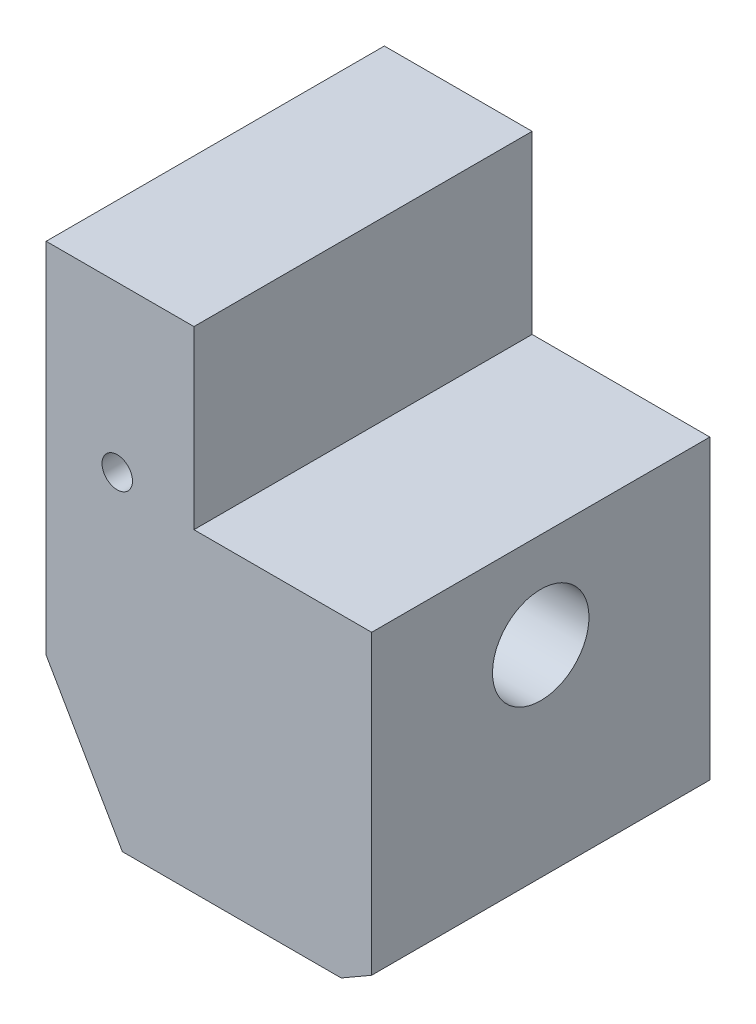
SolidWorks part; units mm, degrees
ref_plane "Front Plane" through (0, 0, 0) normal (0, 0, 1) x (1, 0, 0)
ref_plane "Top Plane" through (0, 0, 0) normal (0, 1, 0) x (1, 0, 0)
ref_plane "Right Plane" through (0, 0, 0) normal (1, 0, 0) x (0, 0, -1)
sketch "Sketch1" plane through (0, 0, 0) normal (1, 0, 0) x (0, 0, -1)
  line L1 (-16.65, 24.15) -> (16.65, 24.15)
  line L2 (-16.65, 24.15) -> (-16.65, -24.15)
  line L3 (-16.65, -24.15) -> (16.65, -24.15)
  line L4 (16.65, 24.15) -> (16.65, -24.15)
  line L5 (-16.65, 24.15) -> (16.65, -24.15) construction
  line L6 (-16.65, -24.15) -> (16.65, 24.15) construction
  point P0 (0, 0)
  dimension "D1" = 48.3
  dimension "D2" = 33.3
extrude "Boss-Extrude1" add sketch "Sketch1" along normal blind 9.55
sketch "Sketch2" plane through (0, 0, 0) normal (-1, 0, 0) x (0, 0, 1)
  line L0 (0, 24.15) -> (0, 19.15) construction
  line L3 (-16.65, 24.15) -> (16.65, 24.15) construction
  line L4 (0, 19.15) -> (0, -19.451) construction
  line L5 (0, -19.451) -> (0, -24.15) construction
  line L6 (16.65, -24.15) -> (-16.65, -24.15) construction
  line L7 (0, 19.15) -> (-5.65, 19.15)
  line L8 (-5.65, 19.15) -> (-5.65, 5.45)
  line L9 (-5.65, 5.45) -> (-11.65, -0.9874)
  line L10 (-11.65, -0.9874) -> (-11.65, -9.1)
  line L11 (-11.65, -9.1) -> (-10.5771, -10.1)
  line L12 (-10.5771, -10.1) -> (10.5771, -10.1)
  line L13 (11.65, -9.1) -> (10.5771, -10.1)
  line L14 (11.65, -0.9874) -> (11.65, -9.1)
  line L15 (5.65, 5.45) -> (11.65, -0.9874)
  line L16 (5.65, 5.45) -> (5.65, 11.45)
  line L17 (5.65, 11.45) -> (4.5, 12.6)
  line L18 (4.5, 12.6) -> (4.5, 19.15)
  line L19 (4.5, 19.15) -> (0, 19.15)
  point P16 (0, -10.1)
  dimension "D1" = 5
  dimension "D2" = 4.699
  dimension "D3" = 11.65
  dimension "D4" = 15.55
  dimension "D5" = 5.65
  dimension "D6" = 13.7
  dimension "D7" = 8.8
  dimension "D8" = 1
  dimension "D9" = 6
  dimension "D10" = 7.15
  dimension "D11" = 4.5
extrude "Cut-Extrude1" cut sketch "Sketch2" against normal blind 5
sketch "Sketch3" plane through (5, 0, 0) normal (-1, 0, 0) x (0, 0, 1)
  line L0 (-5.65, 19.15) -> (4.5, 19.15)
  line L1 (4.5, 19.15) -> (4.5, 12.6)
  line L2 (4.5, 12.6) -> (5.65, 11.45)
  line L3 (5.65, 11.45) -> (5.65, 5.45)
  line L4 (5.65, 5.45) -> (-5.65, 5.45)
  line L5 (-5.65, 5.45) -> (-5.65, 19.15)
extrude "Cut-Extrude2" cut sketch "Sketch3" against normal blind 4.5
sketch "Sketch5" plane through (9.55, 0, 0) normal (1, 0, 0) x (0, 0, -1)
  line L1 (-16.65, 24.15) -> (16.65, 24.15)
  line L2 (-16.65, 24.15) -> (-16.65, -24.15)
  line L3 (-16.65, -24.15) -> (16.65, -24.15)
  line L4 (16.65, 24.15) -> (16.65, -24.15)
  line L5 (-16.65, 24.15) -> (16.65, -24.15) construction
  line L6 (-16.65, -24.15) -> (16.65, 24.15) construction
  point P0 (0, 0)
extrude "Boss-Extrude3" add sketch "Sketch5" along normal blind 22.5
sketch "Sketch6" plane through (5, 0, 0) normal (-1, 0, 0) x (0, 0, 1)
  line L0 (0, 5.45) -> (0, -2.575) construction
  line L1 (-5.65, 5.45) -> (5.65, 5.45) construction
  line L2 (0, 1.45) -> (5.4752, 1.45) construction
  circle A0 centre (0, -2.575) radius 4.025
  dimension "D2" = 8.05
  dimension "D1" = 4
extrude "Cut-Extrude3" cut sketch "Sketch6" against normal blind 12
sketch "Sketch7" plane through (17, 0, 0) normal (-1, 0, 0) x (0, 0, 1)
  circle A0 centre (0, -2.575) radius 4.75
  dimension "D1" = 9.5
extrude "Cut-Extrude4" cut sketch "Sketch7" against normal up to surface (15.05 mm away) up to face at (32.05, 0, 0)
sketch "Sketch27" plane through (0, 0, 5.65) normal (0, 0, -1) x (-1, 0, 0)
  line L0 (-9.5, 5.45) -> (-9.5, 11.45) construction
  line L1 (-9.5, 5.45) -> (-5, 5.45) construction
  circle A0 centre (-7, 7.95) radius 1.5
  dimension "D1" = 3
  dimension "D2" = 2.5
  dimension "D3" = 2.5
extrude "Cut-Extrude6" cut sketch "Sketch27" against normal through all both and the other way through all
ref_plane "Plane1" through (18.4698, -31.9906, 0) normal (0.5, -0.866, 0) x (0, 0, -1)
sketch "Sketch28" plane through (0, 0, 0) normal (0, 0, 1) x (1, 0, 0)
  line L0 (32.05, -2.575) -> (17, -2.575) construction
  line L1 (32.05, -7.325) -> (32.05, 2.175) construction
  line L2 (17, -6.6) -> (17, 1.45) construction
  line L3 (17, -2.575) -> (17, -6.6) construction
  line L4 (17, -7.325) -> (17, 2.175) construction
  line L5 (17, -6.6) -> (13, -6.6) construction
  line L6 (13, -6.6) -> (25.3619, -28.0114)
  line L7 (3.2039, -40.8043) -> (33.7356, -23.1768) construction
  line L8 (13, -6.6) -> (10.75, -2.7029)
  dimension "D1" = 4.025
  dimension "D2" = 4
  dimension "D3" = 60
  dimension "D4" = 180
  dimension "D5" = 4.5
sketch "Sketch29" plane through (0, 0, 0) normal (0, 0, 1) x (1, 0, 0)
  line L0 (32.05, -2.575) -> (17, -2.575) construction
  line L1 (32.05, -7.325) -> (32.05, 2.175) construction
  line L2 (19, -16.9923) -> (25.3619, -28.0114)
  line L3 (17, -2.575) -> (17, -6.6) construction
  line L4 (3.2039, -40.8043) -> (33.7356, -23.1768) construction
  line L5 (17, -6.6) -> (13, -6.6) construction
  line L6 (13, -6.6) -> (19, -16.9923) construction
  line L8 (13, -6.6) -> (25.3619, -28.0114) construction
  dimension "D1" = 4.025
  dimension "D2" = 4
  dimension "D3" = 12
  dimension "D4" = 60
sketch "Sketch30" plane through (18.4698, -31.9906, 0) normal (0.5, -0.866, 0) x (0, 0, -1)
  circle A0 centre (0, 7.9583) radius 4
  dimension "D1" = 8
sweep "Cut-Sweep1" cut profiles "Sketch30" path "Sketch28"
sketch "Sketch31" plane through (18.4698, -31.9906, 0) normal (0.5, -0.866, 0) x (0, 0, -1)
  circle A0 centre (0, 7.9583) radius 5
  dimension "D1" = 10
sweep "Cut-Sweep2" cut profiles "Sketch31" path "Sketch29"
chamfer "Chamfer1" distance 13 angle 30 1 edges at (0, -24.15, 0) first distance on face at (0, 2.7396, 0.75)
chamfer "Chamfer2" distance 10 angle 60 1 edges at (32.05, 24.15, 0) first distance on face at (16.025, 24.15, 0)
chamfer "Chamfer3" distance 3 angle 30 1 edges at (32.05, -24.15, 0) first distance on face at (28.906, -24.15, 0)
sketch "Croquis2" plane through (0, 0, 16.65) normal (0, 0, 1) x (1, 0, 0)
  line L0 (32.05, 6.8295) -> (14.55, 6.8295)
  line L1 (14.55, 6.8295) -> (14.55, 24.15)
  line L2 (22.05, 24.15) -> (0, 24.15) construction
  line L3 (14.55, 24.15) -> (32.05, 24.15)
  line L4 (32.05, 24.15) -> (32.05, 6.8295)
  dimension "D1" = 17.5
  dimension "D2" = 17.5
extrude "Cortar-Extruir1" cut sketch "Croquis2" against normal blind 48
